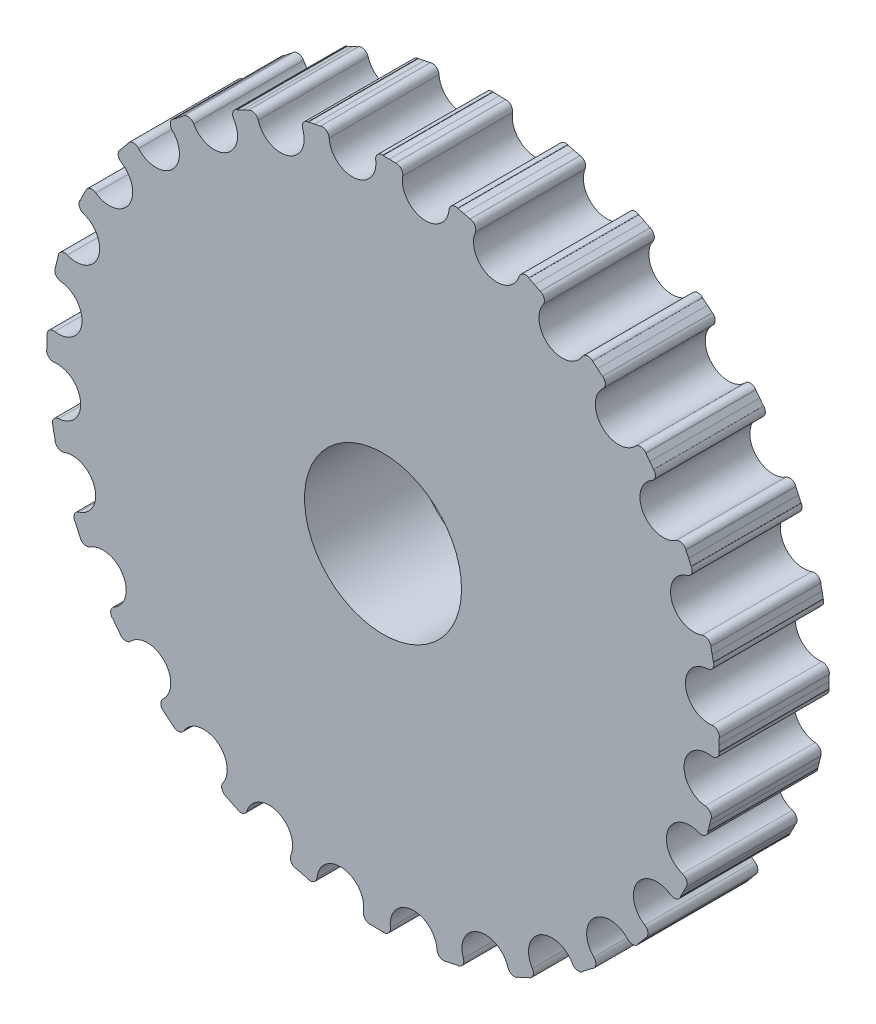
SolidWorks part; units mm, degrees
material "PE High Density"
ref_plane "Front Plane" through (0, 0, 0) normal (0, 0, 1) x (1, 0, 0)
ref_plane "Top Plane" through (0, 0, 0) normal (0, 1, 0) x (1, 0, 0)
ref_plane "Right Plane" through (0, 0, 0) normal (1, 0, 0) x (0, 0, -1)
sketch "PD" plane through (0, 0, 0) normal (0, 0, 1) x (1, 0, 0)
  circle A0 centre (0, 0) radius 22.2817
  circle A1 centre (0, 0) radius 5
  dimension "PD" = 44.5634
  dimension "D1" = 10
extrude "half width" add sketch "PD" along normal blind 7
sketch "Sketch3" plane through (0, 0, 7) normal (0, 0, 1) x (1, 0, 0)
  line L0 (0, 0) -> (0, 21.4117) construction
  line L1 (0, 21.4117) -> (0.827, 21.4117)
  line L2 (0, 0) -> (2.7204, 20.6634) construction
  line L3 (0, 21.4117) -> (0, 22.2817)
  line L4 (5.5418, 20.6821) -> (5.7669, 21.5225)
  line L5 (5.5418, 20.6821) -> (4.743, 20.8961)
  line L6 (2.7204, 20.6634) -> (2.9083, 22.0911) construction
  arc A0 (0.827, 21.4117) -> (1.251, 20.9104) centre (0.827, 20.9817) cw
  arc A1 (1.251, 20.9104) -> (4.2036, 20.5217) centre (2.7204, 20.6634) ccw
  circle A2 centre (0, 0) radius 22.2817 construction
  arc A3 (0, 22.2817) -> (5.7669, 21.5225) centre (0, 0) cw
  arc A4 (4.743, 20.8961) -> (4.2036, 20.5217) centre (4.6317, 20.4808) ccw
  point P8 (2.5259, 19.1861)
  dimension "D1" = 0.43
  dimension "D2" = 1.49
  dimension "D5" = 2.93
  dimension "D3" = 0.87
  dimension "D4" = 7.5
extrude "Teeth " cut sketch "Sketch3" against normal up to surface (7 mm away) up to face at (22.2817, 0, 0)
pattern_circular "CirPattern1" count 28 over 360 about axis through (0, 0, 7) along (0, 0, 1) of "Teeth "
equation "\"n\"= 28"
equation "\"p\"= 5'pitch"
equation "\"pd\"= \"n\" * \"p\" / pi'pitch diameter"
equation "\"PD@PD\"=\"pd\""
equation "\"D1@CirPattern1\"=\"n\""
equation "\"Bolt diameter\"= 3mm"
